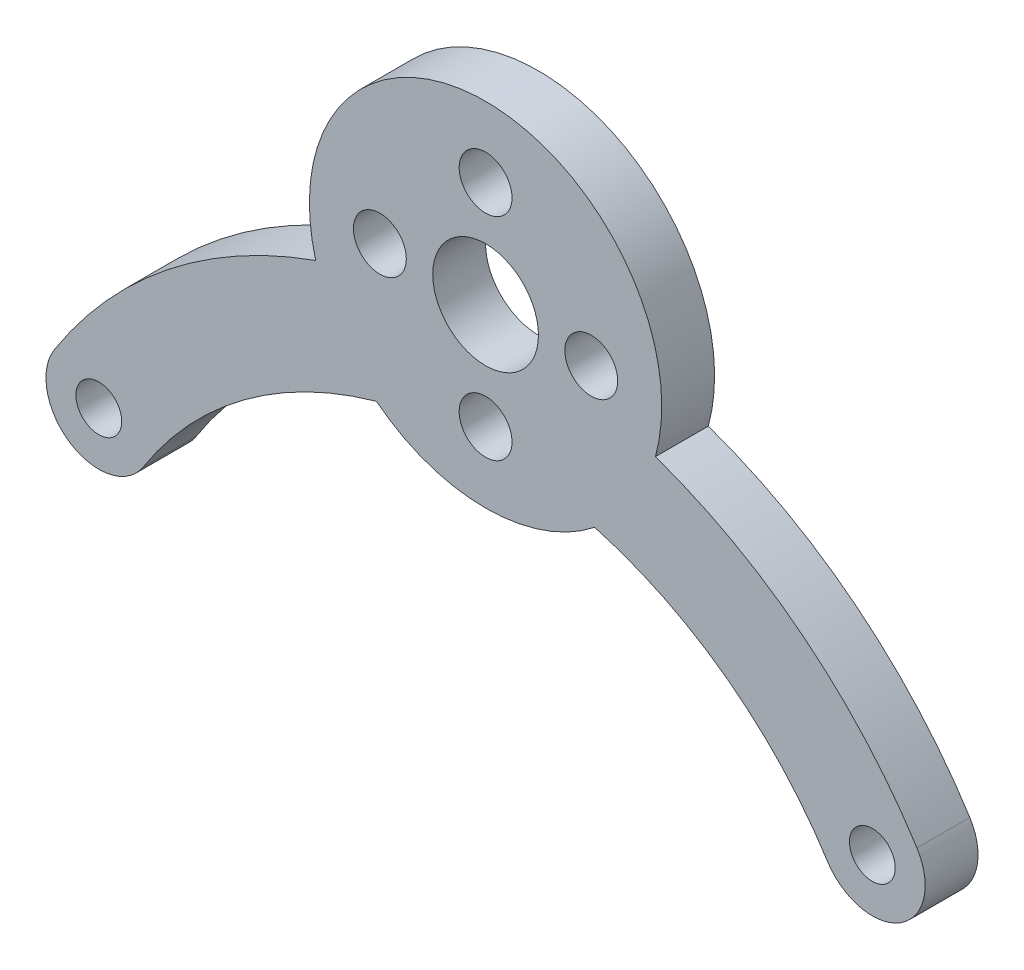
SolidWorks part; units mm, degrees
ref_plane "Front" through (0, 0, 0) normal (0, 0, 1) x (1, 0, 0)
ref_plane "Top" through (0, 0, 0) normal (0, 1, 0) x (1, 0, 0)
ref_plane "Right" through (0, 0, 0) normal (1, 0, 0) x (0, 0, -1)
sketch "Esquisse1" plane through (0, 0, 0) normal (0, 0, 1) x (1, 0, 0)
  line L0 (0, 0) -> (0, 30) construction
  line L1 (0, 30) -> (0, 40) construction
  line L2 (26.1155, 12.6087) -> (20.7123, 10)
  line L3 (20.7123, 10) -> (0, 0) construction
  line L4 (-26.1155, 12.6087) -> (-20.7123, 10)
  arc A0 (9.6425, 27.35) -> (-9.6425, 27.35) centre (0, 30) ccw
  arc A1 (-20.7123, 10) -> (20.7123, 10) centre (0, 0) cw
  arc A2 (9.6425, 27.35) -> (26.1155, 12.6087) centre (0, 0) cw
  arc A3 (-9.6425, 27.35) -> (-26.1155, 12.6087) centre (0, 0) ccw
  dimension "D2" = 23
  dimension "D1" = 10
  dimension "D3" = 30
  dimension "D4" = 6
  dimension "D5" = 10
extrude "Boss.-Extru.1" add sketch "Esquisse1" along normal blind 3
sketch "Esquisse3" plane through (0, 0, 3) normal (0, 0, 1) x (1, 0, 0)
  circle A0 centre (0, 30) radius 10
  arc A1 (9.6425, 27.35) -> (-9.6425, 27.35) centre (0, 30) ccw construction
extrude "Boss.-Extru.2" add sketch "Esquisse3" against normal up to vertex (3 mm away) up to point (26.1155, 12.6087, 0)
fillet "Congé1" radius 3 4 edges at (-26.1155, 12.6087, 1.5) (-20.7123, 10, 1.5) (20.7123, 10, 1.5) (26.1155, 12.6087, 1.5)
sketch "Esquisse2" plane through (0, 0, 3) normal (0, 0, 1) x (1, 0, 0)
  line L0 (0, 30) -> (6, 30) construction
  circle A0 centre (0, 30) radius 3
  circle A1 centre (6, 30) radius 1.5
  circle A2 centre (0, 24) radius 1.5
  circle A3 centre (-6, 30) radius 1.5
  circle A4 centre (0, 36) radius 1.5
  point P5 (-0.5312, 37.7009)
  point P6 (0, 30)
  point P14 (0, 30)
  dimension "D1" = 6
  dimension "D2" = 3
  dimension "D3" = 6
  dimension "D4" = 4
extrude "Enlèv. mat.-Extru.1" cut sketch "Esquisse2" against normal through all both and the other way through all
sketch "Esquisse4" plane through (0, 0, 3) normal (0, 0, 1) x (1, 0, 0)
  circle A0 centre (21.9532, 13.9305) radius 1.3
  circle A1 centre (-21.9532, 13.9305) radius 1.3
  dimension "D1" = 2.6
extrude "Enlèv. mat.-Extru.2" cut sketch "Esquisse4" against normal through all both and the other way through all
